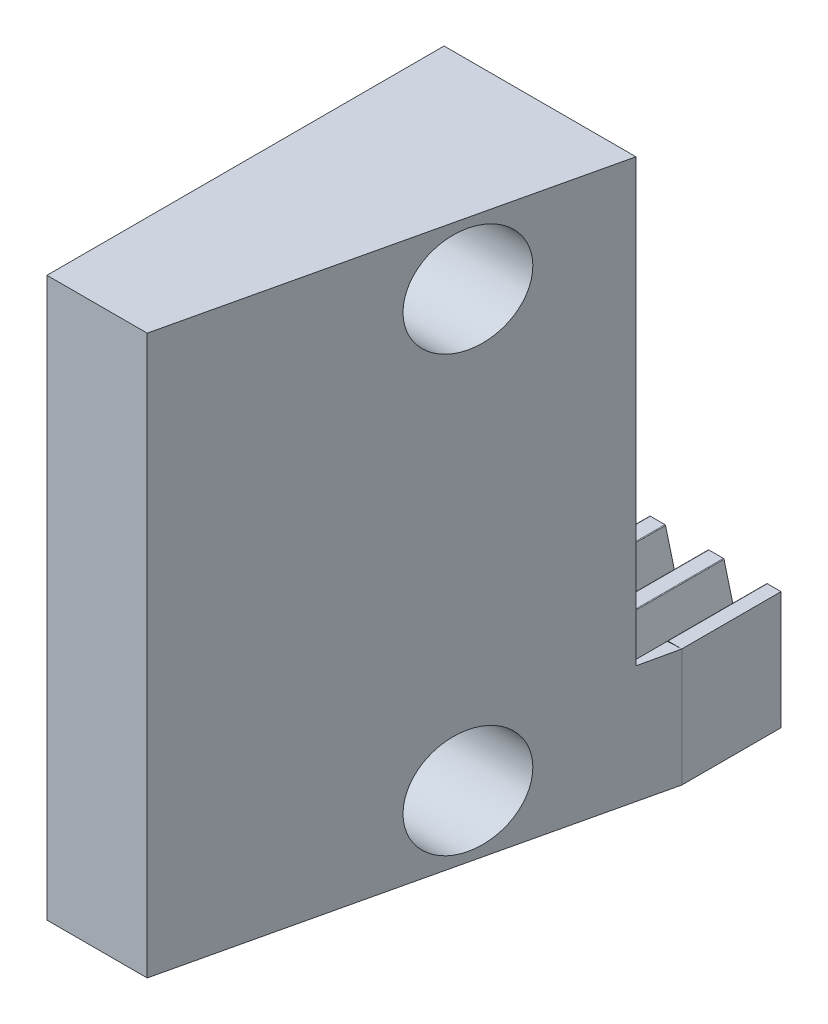
SolidWorks part; units mm, degrees
extrude "Blank" add sketch "BlankSke" against normal blind 8
sketch "BlankSke" plane through (0, 0, 0) normal (0, 0, 1) x (1, 0, 0)
  line L1 (0, 0) -> (50, 0)
  line L2 (0, 0) -> (0, 9.5)
  line L3 (0, 9.5) -> (50, 9.5)
  line L4 (50, 0) -> (50, 9.5)
  dimension "Length" = 50
ref_plane "Plane1" through (0, 0, 0) normal (0, 0, 1) x (1, 0, 0)
ref_plane "Plane2" through (0, 0, 0) normal (0, 1, 0) x (1, 0, 0)
ref_plane "Plane3" through (0, 0, 0) normal (1, 0, 0) x (0, 0, -1)
other "Configuration Table"
sketch "HoldingSke" plane through (0, 0, 0) normal (0, 1, 0) x (1, 0, 0)
  line L0 (0, 0) -> (0.0928, 0.6602)
  line L1 (-15, 0) -> (100, 0) construction
  line L2 (0, 0) -> (-2.1039, 2.3779)
  line L3 (0, 0) -> (-11.863, 4.5341)
  line L4 (0, 0) -> (8.4473, 1.7955)
  line L5 (0, 0) -> (-23.7986, -8.8762)
  line L6 (0, 0) -> (-10.5278, -7.1032)
  line L9 (-67.7845, 28.3722) -> (-19.3772, 40.8912)
  line L10 (-76.2, 3.8779) -> (-68.2, 3.8779)
  line L11 (0, 0) -> (-8, 0)
  line L12 (-76.2, 101.6) -> (-76.147, 101.6)
  line L13 (24.9733, 27.94) -> (52.9518, 28.4284)
  line L14 (24.9733, 27.94) -> (24.9743, 27.94)
  line L15 (24.9733, 27.94) -> (100.4006, 29.5858)
  circle A0 centre (0, 0) radius 19.05
  circle A1 centre (0, 0) radius 4
  circle A2 centre (0, 0) radius 12.7
  dimension "Num_teeth" = 12
  dimension "Width" = 8
  dimension "Length" = 50
  dimension "Pitch_height" = 8
sketch "TooCutSkeIll" plane through (0, 0, 0) normal (0, 0, 1) x (1, 0, 0)
  line L0 (-1.7134, 9.455) -> (-0.9251, 6.4069)
  line L1 (-0.5611, 6.125) -> (0.5611, 6.125)
  line L2 (0.9251, 6.4069) -> (1.7134, 9.455)
  line L3 (50, 9.5) -> (0, 9.5) construction
  line L4 (0, 0) -> (0, 64.897) construction
  line L5 (-13.208, 8) -> (12.954, 8) construction
  line L6 (0, 0) -> (50, 0) construction
  line L7 (1.3371, 8) -> (1.3371, 48.7463) construction
  line L8 (-1.3371, 8) -> (-1.3371, 48.7463) construction
  line L9 (1.7715, 9.5) -> (1.7715, 9.5254)
  line L10 (-1.7715, 9.5) -> (-1.7715, 9.5254)
  line L11 (-1.7715, 9.5254) -> (1.7715, 9.5254)
  arc A0 (0.5611, 6.125) -> (0.9251, 6.4069) centre (0.5611, 6.501) ccw
  arc A1 (-0.9251, 6.4069) -> (-0.5611, 6.125) centre (-0.5611, 6.501) ccw
  arc A2 (1.7715, 9.5) -> (1.7134, 9.455) centre (1.7715, 9.44) ccw
  arc A3 (-1.7134, 9.455) -> (-1.7715, 9.5) centre (-1.7715, 9.44) ccw
  dimension "Addendum_plus" = 1.5254
  dimension "Pitch_height" = 8
  dimension "Pressure_angle" = 14.5
  dimension "Gap_width" = 2.6742
  dimension "Dedendum" = 1.875
extrude "ToothCutIll" cut sketch "TooCutSkeIll" against normal through all
sketch "TooCutSkeSim" plane through (0, 0, 0) normal (0, 0, 1) x (1, 0, 0)
  line L0 (0.8522, 6.125) -> (-0.8522, 6.125)
  line L1 (1.7316, 9.5254) -> (0.8522, 6.125)
  line L2 (0, 17.4625) -> (0, 53.467) construction
  line L3 (1.7316, 9.5254) -> (-1.7316, 9.5254)
  line L6 (-1.7316, 9.5254) -> (-0.8522, 6.125)
  line L9 (-1.3371, 8) -> (1.3371, 8) construction
  line L10 (0, 0) -> (50, 0) construction
  line L11 (1.3371, 8) -> (1.3371, 53.467) construction
  line L12 (-1.3371, 8) -> (-1.3371, 53.467) construction
  dimension "Addendum_plus" = 1.5254
  dimension "Pitch_height" = 8
  dimension "Pressure_angle" = 14.5
  dimension "Gap_width" = 2.6742
  dimension "Dedendum" = 1.875
extrude "ToothCutSim" cut sketch "TooCutSkeSim" against normal through all
pattern_linear "TeethCuts" count 12 spacing 4.7124 along (1, 0, 0) of "ToothCutIll", "ToothCutSim"
sketch "Sketch3" plane through (50, 0, 0) normal (1, 0, 0) x (0, 0, -1)
  line L1 (0, 9.5) -> (8, 9.5)
  line L2 (0, 9.5) -> (0, 0)
  line L3 (0, 0) -> (8, 0)
  line L4 (8, 9.5) -> (8, 0)
extrude "Boss-Extrude2" [suppressed] add sketch "Sketch3" along normal blind 15
sketch "Sketch5" [suppressed] plane through (0, 9.5, 0) normal (0, 1, 0) x (1, 0, 0)
  line L1 (39.4241, 8) -> (55, 8)
  line L2 (39.4241, 8) -> (39.4241, 0)
  line L3 (39.4241, 0) -> (55, 0)
  line L4 (55, 8) -> (55, 0)
extrude "Boss-Extrude3" [suppressed] add sketch "Sketch5" along normal blind 30
sketch "Sketch7" [suppressed] plane through (0, 0, 0) normal (0, 1, 0) x (1, 0, 0)
  line L4 (65, 0) -> (39.4241, 0)
  line L5 (0, 0) -> (65, 0) construction
  line L9 (39.4241, 0) -> (39.4241, -25)
  line L10 (39.4241, -25) -> (47.2121, -25)
  line L11 (47.2121, -25) -> (65, 0)
extrude "Boss-Extrude5" [suppressed] add sketch "Sketch7" along normal blind 39.5
sketch "Sketch8" [suppressed] plane through (0, 0, -8) normal (0, 0, -1) x (-1, 0, 0)
  line L1 (-39.4241, 9.5) -> (-55, 9.5)
  line L2 (-39.4241, 9.5) -> (-39.4241, 39.5)
  line L3 (-39.4241, 39.5) -> (-55, 39.5)
  line L4 (-55, 9.5) -> (-55, 39.5)
extrude "Cut-Extrude1" [suppressed] cut sketch "Sketch8" against normal blind 11
sketch "Sketch9" [suppressed] plane through (0, 0, 25) normal (0, 0, 1) x (1, 0, 0)
  line L1 (39.4241, 39.5) -> (65, 39.5)
  line L2 (39.4241, 39.5) -> (39.4241, 0)
  line L3 (39.4241, 0) -> (65, 0)
  line L4 (65, 39.5) -> (65, 0)
extrude "Cut-Extrude2" [suppressed] cut sketch "Sketch9" against normal blind 25
sketch "Sketch10" [suppressed] plane through (0, 9.5, 0) normal (0, 1, 0) x (1, 0, 0)
  line L1 (65, 0) -> (48.8489, 0)
  line L2 (65, 0) -> (65, 8)
  line L3 (65, 8) -> (48.8489, 8)
  line L4 (48.8489, 0) -> (48.8489, 8)
extrude "Boss-Extrude6" [suppressed] add sketch "Sketch10" along normal blind 35.5
sketch "Sketch12" [suppressed] plane through (0, 45, 0) normal (0, 1, 0) x (1, 0, 0)
  line L0 (48.8489, 0) -> (65, 0)
  line L1 (48.8489, 0) -> (48.8489, -25)
  line L2 (48.8489, -25) -> (56.9245, -25)
  line L3 (56.9245, -25) -> (65, 0)
extrude "Boss-Extrude7" [suppressed] add sketch "Sketch12" against normal blind 45
sketch "Sketch13" [suppressed] plane through (0, 0, -8) normal (0, 0, -1) x (-1, 0, 0)
  line L1 (-48.8489, 9.5) -> (-65, 9.5)
  line L2 (-48.8489, 9.5) -> (-48.8489, 45)
  line L3 (-48.8489, 45) -> (-65, 45)
  line L4 (-65, 9.5) -> (-65, 45)
extrude "Cut-Extrude3" [suppressed] cut sketch "Sketch13" against normal blind 11
sketch "Sketch14" [suppressed] plane through (48.8489, 0, 0) normal (-1, 0, 0) x (0, 0, 1)
  line L1 (-8, 45) -> (25, 45) construction
  line L2 (0, 0) -> (25, 0) construction
  circle A0 centre (14, 40) radius 1.75
  circle A1 centre (14, 5) radius 1.75
  dimension "D2" = 5
  dimension "D1" = 5
extrude "Cut-Extrude4" [suppressed] cut sketch "Sketch14" against normal blind 21
sketch "Sketch16" plane through (0, 0, 0) normal (0, -1, 0) x (1, 0, 0)
  line L0 (50, 0) -> (33.849, 0)
  line L1 (0, 0) -> (50, 0) construction
  line L2 (33.849, 0) -> (33.849, 35)
  line L3 (33.849, 35) -> (41.925, 35)
  line L4 (41.925, 35) -> (50, 0)
extrude "Boss-Extrude8" add sketch "Sketch16" against normal blind 45
sketch "Sketch17" plane through (0, 0, 0) normal (0, 0, -1) x (-1, 0, 0)
  line L0 (-50, 9.5) -> (-48.8373, 9.455)
  line L1 (-48.8373, 9.455) -> (-47.9761, 6.125)
  line L2 (-47.9761, 6.125) -> (-46.2717, 6.125)
  line L3 (-46.2717, 6.125) -> (-45.4105, 9.455)
  line L4 (-45.4105, 9.455) -> (-44.1249, 9.455)
  line L5 (-44.1249, 9.455) -> (-43.2637, 6.125)
  line L6 (-43.2637, 6.125) -> (-41.5593, 6.125)
  line L7 (-41.5593, 6.125) -> (-40.6981, 9.455)
  line L8 (-40.6981, 9.455) -> (-39.4125, 9.455)
  line L9 (-39.4125, 9.455) -> (-38.5513, 6.125)
  line L10 (-38.5513, 6.125) -> (-36.8469, 6.125)
  line L11 (-36.8469, 6.125) -> (-35.9857, 9.455)
  line L12 (-35.9857, 9.455) -> (-34.7001, 9.455)
  line L13 (-34.7001, 9.455) -> (-33.8389, 6.125)
  line L14 (-33.8389, 6.125) -> (-33.849, 45)
  line L15 (-33.849, 45) -> (-50, 45)
  line L16 (-50, 45) -> (-50, 9.5)
extrude "Cut-Extrude5" cut sketch "Sketch17" against normal blind 3
sketch "Sketch20" plane through (33.849, 0, 0) normal (-1, 0, 0) x (0, 0, 1)
  line L0 (35, 45) -> (3, 45) construction
  line L1 (35, 0) -> (0, 0) construction
  circle A0 centre (14, 40) radius 4.25
  circle A1 centre (14, 5) radius 4.25
  dimension "D1" = 5
  dimension "D2" = 5
extrude "Cut-Extrude6" cut sketch "Sketch20" against normal blind 25
equation "' \"Module@HoldingSke\" = 6.35"
equation "' \"Num_teeth@HoldingSke\" = 12"
equation "' \"Ap@HoldingSke\" =  20"
equation "' \"Ap@HoldingSke\" = 20"
equation "' \"Width@HoldingSke\" = 0.25 * 25.4"
equation "' \"Show_teeth@HoldingSke\" = 500"
equation "' \"Backlash@HoldingSke\" = 0.009 * 25.4"
equation "' \"Addendum_fac@HoldingSke\" = 1.0"
equation "' \"Dedendum_fac@HoldingSke\" = 1.25"
equation "' \"Dedendum_add@HoldingSke\" = 0.00005 * 25.4"
equation "' \"Clearance_fac@HoldingSke\" = 0.25"
equation "' \"Pitch_height@HoldingSke\" = 1 * 25.4"
equation "' \"Length@HoldingSke\" = 4.71 * 25.4"
equation "\"Pitch@HoldingSke\" = 1 / \"Module@HoldingSke\""
equation "\"MPH@HoldingSke\" = \"Dedendum_fac@HoldingSke\" / \"Pitch@HoldingSke\" + 2 * \"Dedendum_add@HoldingSke\" + 0.002 * 25.4"
equation "\"MPH@HoldingSke\" = ((sgn( \"MPH@HoldingSke\" - \"Pitch_height@HoldingSke\")+1)*( \"MPH@HoldingSke\" - \"Pitch_height@HoldingSke\"))/2 + \"Pitch_height@HoldingSke\""
equation "\"Blank_height@BlankSke\" = \"Pitch_height@HoldingSke\" + \"Addendum_fac@HoldingSke\"  / \"Pitch@HoldingSke\" "
equation "\"Length@BlankSke\" =  \"Length@HoldingSke\""
equation "\"Face_width@Blank\" = \"Width@HoldingSke\""
equation "\"Pressure_angle@TooCutSkeIll\" = \"Ap@HoldingSke\""
equation "\"Addendum_plus@TooCutSkeIll\" =  \"Addendum_fac@HoldingSke\"  / \"Pitch@HoldingSke\" + 0.001 *25.4"
equation "\"Dedendum@TooCutSkeIll\" = \"Dedendum_fac@HoldingSke\"  / \"Pitch@HoldingSke\""
equation "\"Pitch_height@TooCutSkeIll\" =  \"MPH@HoldingSke\""
equation "\"Gap_width@TooCutSkeIll\" = 3.14159265 / 2 / \"Pitch@HoldingSke\" + 6 * \"Backlash@HoldingSke\""
equation "\"Pressure_angle@TooCutSkeSim\" = \"Ap@HoldingSke\""
equation "\"Addendum_plus@TooCutSkeSim\" =  \"Addendum_fac@HoldingSke\"  / \"Pitch@HoldingSke\" + 0.001 * 25.4"
equation "\"Dedendum@TooCutSkeSim\" = \"Dedendum_fac@HoldingSke\"  / \"Pitch@HoldingSke\""
equation "\"Pitch_height@TooCutSkeSim\" =  \"MPH@HoldingSke\""
equation "\"Gap_width@TooCutSkeSim\" = 3.14159265 / 2 / \"Pitch@HoldingSke\" + 6 * \"Backlash@HoldingSke\""
equation "\"Root_fillet@TooCutSkeIll\" = \"Clearance_fac@HoldingSke\" / \"Pitch@HoldingSke\" + \"Dedendum_add@HoldingSke\""
equation "\"Break_rad@TooCutSkeIll\" = 0.02 / \"Pitch@HoldingSke\" * 2"
equation "\"Linear_pitch@TeethCuts\" = 3.14159265 / \"Pitch@HoldingSke\""
equation "\"Num_teeth@HoldingSke\" = int( ( \"Length@HoldingSke\" + 0 ) / (3.14159265 / \"Pitch@HoldingSke\")) + 0.9999  + 1"
equation " \"Num_teeth@TeethCuts\" = int( \"Show_teeth@HoldingSke\" ) + 1"
equation " \"Num_teeth@TeethCuts\" = ((sgn( \"Num_teeth@TeethCuts\" - \"Num_teeth@HoldingSke\" )-1)*( \"Num_teeth@TeethCuts\" - \"Num_teeth@HoldingSke\" ))/-2+ \"Num_teeth@HoldingSke\""
equation " \"Num_teeth@TeethCuts\" = ((sgn( \"Num_teeth@TeethCuts\" - 2.0)+1)*( \"Num_teeth@TeethCuts\" - 2.0))/2 +2.0"
